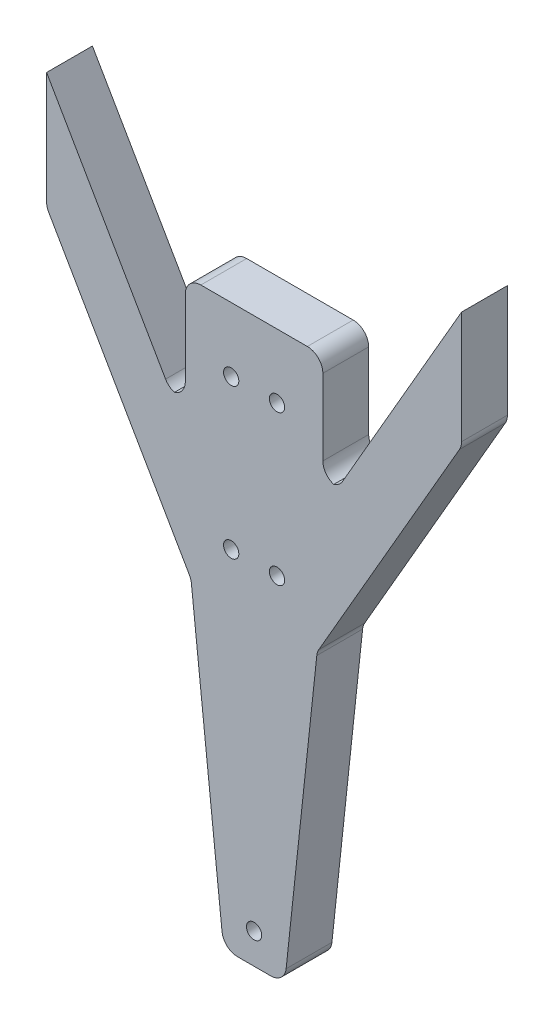
SolidWorks part; units mm, degrees
ref_plane "Plan de face" through (0, 0, 0) normal (0, 0, 1) x (1, 0, 0)
ref_plane "Plan de dessus" through (0, 0, 0) normal (0, 1, 0) x (1, 0, 0)
ref_plane "Plan de droite" through (0, 0, 0) normal (1, 0, 0) x (0, 0, -1)
sketch "Sketch1" plane through (0, 0, 0) normal (0, 0, 1) x (1, 0, 0)
  line L19 (27.5105, 50) -> (67.925, 120)
  line L21 (67.925, 81.9) -> (20.64, 0)
  line L23 (20.64, 0) -> (10, -99.4323)
  line L24 (10, -99.4323) -> (-10, -99.4323)
  line L25 (-10, -99.4323) -> (-20.64, 0)
  line L26 (-20.64, 0) -> (-67.925, 81.9)
  line L28 (-67.925, 120) -> (-27.5105, 50)
  line L29 (-20.64, 0) -> (20.64, 0) construction
  line L30 (-67.925, 120) -> (-67.925, 81.9)
  line L31 (67.925, 120) -> (67.925, 81.9)
  line L35 (-27.5105, 50) -> (-22.5105, 50)
  line L36 (27.5105, 50) -> (22.5105, 50)
  line L37 (-22.5105, 50) -> (-22.5105, 85)
  line L38 (-22.5105, 85) -> (22.5105, 85)
  line L39 (22.5105, 85) -> (22.5105, 50)
  point P16 (-25.0105, 50)
  point P18 (0, -99.4323)
  dimension "D1" = 41.28
  dimension "D2" = 19.05
  dimension "D3" = 60
  dimension "D4" = 120
  dimension "D5" = 100
  dimension "D6" = 5
  dimension "D7" = 20
  dimension "D8" = 19.05
  dimension "D9" = 67.925
  dimension "D10" = 5
  dimension "D11" = 35
extrude "Boss-Extrude1" add sketch "Sketch1" along normal blind 15
fillet "Fillet1" radius 5.08 12 edges at (-10, -99.4323, 7.5) (10, -99.4323, 7.5) (20.64, 0, 7.5) (-20.64, 0, 7.5) (67.925, 81.9, 7.5) (-67.925, 81.9, 7.5) (27.5105, 50, 7.5) (22.5105, 50, 7.5) (-27.5105, 50, 7.5) (-22.5105, 50, 7.5) (-22.5105, 85, 7.5) (22.5105, 85, 7.5)
hole_wizard "Ø5.0mm Dowel Hole1" positions "Sketch12" profile "Sketch13" hole size "Ø5.0" standard "ANSI Metric" end condition through all
sketch "Sketch12" plane through (0, 0, 0) normal (0, 0, -1) x (-1, 0, 0)
  line L14 (-7.5, 15) -> (7.5, 15) construction
  point P83 (7.5, 15)
  point P89 (-7.5, 15)
  point P116 (0, 15)
  point P121 (0, 0)
  dimension "D1" = 15
  dimension "D2" = 15
sketch "Sketch13" plane through (-7.5, 15, 0) normal (1, 0, 0) x (0, 1, 0)
  line L0 (0, 0) -> (0, 15)
  line L1 (0, 15) -> (2.5, 15)
  line L2 (2.5, 15) -> (2.5, 0)
  line L5 (2.5, 0) -> (0, 0)
  line L11 (0, -6.35) -> (0, 107.95) construction
  dimension "Thru Hole Dia." = 5
  dimension "Thru Hole Depth" = 15
sketch "Sketch16" plane through (0, 0, 0) normal (0, 0, -1) x (-1, 0, 0)
  circle A0 centre (-7.5, 15) radius 5.5
  circle A1 centre (7.5, 15) radius 5.5
  dimension "D1" = 11
  dimension "D2" = 11
extrude "Cut-Extrude2" cut sketch "Sketch16" against normal blind 5
sketch "Sketch14" plane through (0, 0, 15) normal (0, 0, 1) x (1, 0, 0)
  line L0 (-5.4346, -99.4323) -> (5.4346, -99.4323) construction
  circle A0 centre (0, -89.4323) radius 2.5
  dimension "D1" = 5
  dimension "D2" = 10
extrude "Cut-Extrude1" cut sketch "Sketch14" against normal through all
pattern_linear "LPattern2" count 2 spacing 49 along (0, 1, 0) of "Ø5.0mm Dowel Hole1", "Cut-Extrude2"
